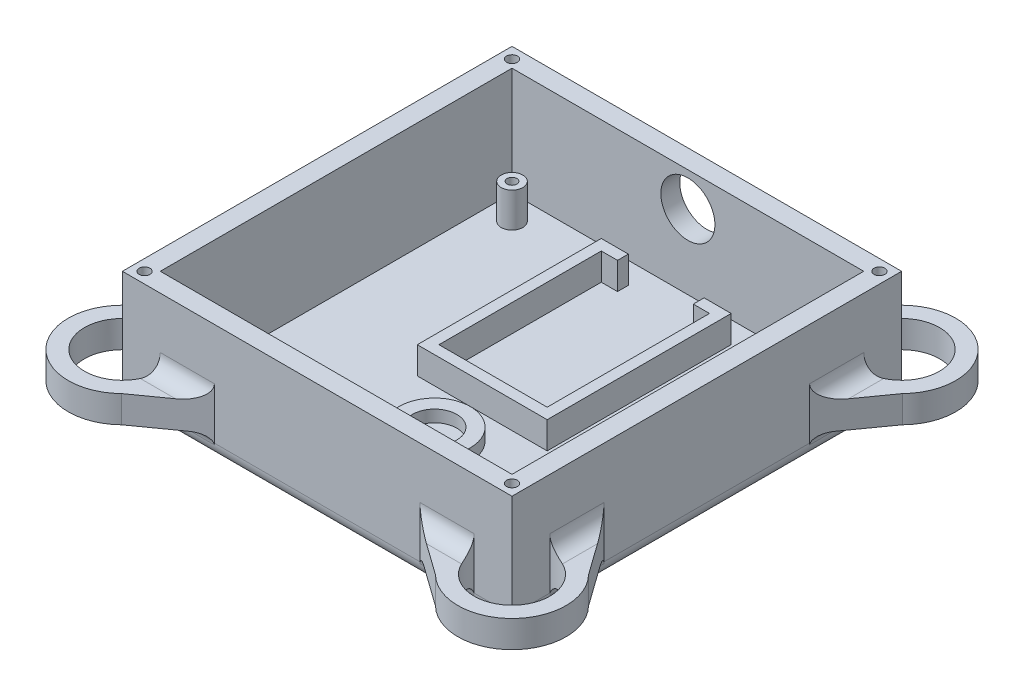
SolidWorks part; units mm, degrees
ref_plane "Front Plane" through (0, 0, 0) normal (0, 0, 1) x (1, 0, 0)
ref_plane "Top Plane" through (0, 0, 0) normal (0, 1, 0) x (1, 0, 0)
ref_plane "Right Plane" through (0, 0, 0) normal (1, 0, 0) x (0, 0, -1)
sketch "Sketch1" plane through (0, 0, 0) normal (0, 1, 0) x (1, 0, 0)
  line L2 (-35, 31) -> (30, 31)
  line L3 (30, 31) -> (30, -34)
  line L5 (-35, -34) -> (30, -34)
  line L6 (-35, 31) -> (-35, -34)
  line L7 (-1, 34.5) -> (33.5, 34.5)
  line L8 (33.5, 34.5) -> (-38.5, 34.5)
  line L9 (-38.5, 34.5) -> (-38.5, -37.5)
  line L11 (33.5, 34.5) -> (33.5, -37.5)
  line L12 (33.5, -37.5) -> (-38.5, -37.5)
  line L13 (0, -34) -> (0, -53.1946) construction
  dimension "D1" = 65
  dimension "D2" = 3.5
  dimension "D3" = 3.5
  dimension "D4" = 65
  dimension "D5" = 3.5
  dimension "D6" = 3.5
extrude "Boss-Extrude1" add sketch "Sketch1" along normal blind 20 contours L6 L2 L3 L5 L12 L11 L7 L8 L9 region at (16.25, 0, -33.4818)
sketch "Sketch2" plane through (0, 0, 0) normal (0, -1, 0) x (1, 0, 0)
  line L1 (-38.5, 37.5) -> (33.5, 37.5)
  line L2 (-38.5, 37.5) -> (-38.5, -34.5)
  line L3 (-38.5, -34.5) -> (33.5, -34.5)
  line L4 (33.5, 37.5) -> (33.5, -34.5)
extrude "Boss-Extrude2" add sketch "Sketch2" along normal blind 2
sketch "Sketch3" plane through (0, 0, 0) normal (0, 1, 0) x (1, 0, 0)
  line L0 (-2.5, 31) -> (-2.5, -34) construction
  line L1 (-35, 31) -> (30, 31) construction
  line L2 (-35, -34) -> (30, -34) construction
  line L3 (-2.5, -34) -> (-2.5, -1.5) construction
  line L4 (-2.5, -1.5) -> (30, -1.5) construction
  line L5 (30, 31) -> (30, -34) construction
  line L6 (30, -1.5) -> (-35, -1.5) construction
  line L7 (-35, 31) -> (-35, -34) construction
  line L8 (-32.5, 28.5) -> (27.5, 28.5) construction
  line L9 (27.5, 28.5) -> (27.5, -31.5) construction
  line L10 (-32.5, -31.5) -> (27.5, -31.5) construction
  line L11 (-32.5, 28.5) -> (-32.5, -31.5) construction
  circle A0 centre (25.5, 26.5) radius 2
  circle A1 centre (25.5, 26.5) radius 0.9
  circle A2 centre (25.5, -29.5) radius 2
  circle A3 centre (25.5, -29.5) radius 0.9
  circle A4 centre (-30.5, -29.5) radius 0.9
  circle A5 centre (-30.5, -29.5) radius 2
  circle A6 centre (-30.5, 26.5) radius 2
  circle A7 centre (-30.5, 26.5) radius 0.9
  point P23 (27.5, -1.5)
  point P28 (-2.5, -31.5)
  point P32 (-2.5, 28.5)
  dimension "D3" = 2
  dimension "D4" = 4
  dimension "D5" = 2
  dimension "D1" = 30
  dimension "D2" = 30
extrude "Boss-Extrude3" add sketch "Sketch3" along normal blind 6.4
sketch "Sketch4" plane through (0, 20, 0) normal (0, 1, 0) x (1, 0, 0)
  line L0 (-2.5, 34.5) -> (-2.5, -37.5) construction
  line L1 (-38.5, 34.5) -> (33.5, 34.5) construction
  line L2 (33.5, -37.5) -> (-38.5, -37.5) construction
  line L3 (-38.5, -1.5) -> (33.5, -1.5) construction
  line L5 (-38.5, 34.5) -> (-38.5, -37.5) construction
  line L7 (-35, 31) -> (-38.5, 34.5) construction
  line L9 (33.5, 34.5) -> (33.5, -37.5) construction
  circle A1 centre (-36.4494, 32.4494) radius 1
  circle A2 centre (31.4494, 32.4494) radius 1
  circle A3 centre (31.4494, -35.4494) radius 1
  circle A4 centre (-36.4494, -35.4494) radius 1
  dimension "D1" = 2.9
extrude "Cut-Extrude1" cut sketch "Sketch4" against normal blind 8
ref_plane "Plane1" through (0, 5, 0) normal (0, -1, 0) x (-1, 0, 0)
sketch "Sketch5" plane through (0, 5, 0) normal (0, 1, 0) x (1, 0, 0)
  line L0 (33.5, 34.5) -> (26.5, 41.1203) construction
  line L1 (33.5, 34.5) -> (26.5, 34.5)
  line L2 (26.5, 34.5) -> (26.5, 41.6414) construction
  line L3 (26.5, 34.5) -> (33.5, 34.5)
  line L5 (33.5, 34.5) -> (33.5, -37.5) construction
  line L6 (26.5, 34.5) -> (23.5, 34.5)
  line L7 (26.5, 41.6414) -> (26.5, 27.5) construction
  line L8 (33.5, 27.5) -> (33.5, 24.5)
  line L9 (-2.5, 38.4614) -> (-2.5, -44.4375) construction
  line L10 (-42.2092, -1.5) -> (36.5358, -1.5) construction
  line L14 (-31.5, 34.5) -> (-28.5, 34.5)
  line L19 (-38.5, 34.5) -> (33.5, 34.5) construction
  line L20 (26.5, 27.5) -> (40.6414, 27.5) construction
  line L21 (26.5, 41.6414) -> (16.5, 34.5)
  line L22 (16.5, 34.5) -> (23.5, 34.5)
  line L23 (40.6414, 27.5) -> (33.5, 17.5)
  line L24 (33.5, 17.5) -> (33.5, 24.5)
  line L25 (-21.5, 34.5) -> (-28.5, 34.5)
  line L26 (-31.5, 41.6414) -> (-21.5, 34.5)
  line L27 (-45.6414, 27.5) -> (-38.5, 17.5)
  line L28 (-38.5, 17.5) -> (-38.5, 24.5)
  line L29 (-38.5, 27.5) -> (-38.5, 24.5)
  line L30 (26.5, -37.5) -> (23.5, -37.5)
  line L31 (16.5, -37.5) -> (23.5, -37.5)
  line L32 (26.5, -44.6414) -> (16.5, -37.5)
  line L33 (40.6414, -30.5) -> (33.5, -20.5)
  line L34 (33.5, -20.5) -> (33.5, -27.5)
  line L35 (33.5, -30.5) -> (33.5, -27.5)
  line L36 (-38.5, -30.5) -> (-38.5, -27.5)
  line L37 (-38.5, -20.5) -> (-38.5, -27.5)
  line L38 (-45.6414, -30.5) -> (-38.5, -20.5)
  line L39 (-31.5, -44.6414) -> (-21.5, -37.5)
  line L40 (-21.5, -37.5) -> (-28.5, -37.5)
  line L41 (-31.5, -37.5) -> (-28.5, -37.5)
  arc A0 (33.5, 27.5) -> (26.5, 34.5) centre (33.5, 34.5) ccw
  arc A1 (40.6414, 27.5) -> (26.5, 41.6414) centre (33.5, 34.5) ccw
  arc A8 (-45.6414, 27.5) -> (-31.5, 41.6414) centre (-38.5, 34.5) cw
  arc A9 (-38.5, 27.5) -> (-31.5, 34.5) centre (-38.5, 34.5) cw
  arc A10 (40.6414, -30.5) -> (26.5, -44.6414) centre (33.5, -37.5) cw
  arc A11 (33.5, -30.5) -> (26.5, -37.5) centre (33.5, -37.5) cw
  arc A12 (-38.5, -30.5) -> (-31.5, -37.5) centre (-38.5, -37.5) ccw
  arc A13 (-45.6414, -30.5) -> (-31.5, -44.6414) centre (-38.5, -37.5) ccw
  dimension "D3" = 7
  dimension "D2" = 7
extrude "Boss-Extrude6" add sketch "Sketch5" along normal blind 2.5 and the other way blind 2.5 contours A9 L29 L28 L27 A8 L26 L25 L14 | A13 L38 L37 L36 A12 L41 L40 L39 | A1 L23 L24 L8 A0 L6 L22 L21 | A11 L35 L34 L33 A10 L32 L31 L30 region at (25, 5, -34.8818) region at (-43.7197, 5, -39.7197) region at (38.7197, 5, 42.7197) region at (-43.7197, 5, 42.7197)
sketch "Sketch10" plane through (0, 0, 0) normal (0, 1, 0) x (1, 0, 0)
  line L0 (-2.5, 31) -> (-2.5, -11.7) construction
  line L1 (-35, 31) -> (30, 31) construction
  line L4 (-35, 31) -> (-35, -34) construction
  line L5 (-35, -1.5) -> (30, -1.5) construction
  line L6 (30, 31) -> (30, -34) construction
  line L13 (-3.9, -19.6536) -> (-3.9, -22.2498)
  line L14 (-1.1, -19.6536) -> (-1.1, -22.2498)
  arc A0 (-1.1, -19.6536) -> (-3.9, -19.6536) centre (-2.5, -15.8) ccw
  arc A1 (-1.1, -22.2498) -> (-3.9, -22.2498) centre (-2.5, -15.8) ccw
  dimension "D2" = 8.2
  dimension "D1" = 13.2
  dimension "D3" = 14.3
extrude "Boss-Extrude7" add sketch "Sketch10" along normal blind 2.2
sketch "Sketch11" plane through (0, 0, 0) normal (0, 1, 0) x (1, 0, 0)
  line L0 (9.5, -1.5) -> (30, -1.5) construction
  line L1 (-12.5, 25) -> (-12.5, -5)
  line L2 (-35, -34) -> (30, -34) construction
  line L3 (-14.5, 27) -> (-14.5, -7)
  line L5 (30, 31) -> (30, -34) construction
  line L6 (-35, 31) -> (30, 31) construction
  line L7 (-12.5, 25) -> (-9.5, 25)
  line L9 (-12.5, -5) -> (7.5, -5)
  line L12 (-14.5, -7) -> (9.5, -7)
  line L13 (9.5, -7) -> (9.5, 27)
  line L14 (9.5, 27) -> (4.5, 27)
  line L15 (4.5, 27) -> (4.5, 25)
  line L16 (7.5, 25) -> (7.5, -5)
  line L17 (-2.5, -5) -> (7.5, -5)
  line L19 (4.5, 25) -> (7.5, 25)
  line L21 (-14.5, 27) -> (-9.5, 27)
  line L22 (-9.5, 27) -> (-9.5, 25)
  line L23 (-9.5, 25) -> (-12.5, 25)
  line L24 (4.5, 25) -> (7.5, 25)
  line L25 (-2.5, -7) -> (-2.5, -34) construction
  dimension "D1" = 30
  dimension "D2" = 6
  dimension "D3" = 10
  dimension "D4" = 2
  dimension "D6" = 2
fillet "Fillet1" radius 3 4 edges at (-2.5, -2, 37.5) (33.5, -2, 1.5) (-2.5, -2, -34.5) (-38.5, -2, 1.5)
extrude "Boss-Extrude8" add sketch "Sketch11" along normal blind 5 contours L22 L21 L3 L12 L13 L14 L15 L19 L16 L9 L1 L7 region at (-12.9162, 0, -10)
fillet "Fillet2" radius 3 8 edges at (-38.5, 7.5, -22.5) (-26.5, 7.5, -34.5) (21.5, 7.5, -34.5) (33.5, 7.5, -22.5) (33.5, 7.5, 25.5) (21.5, 7.5, 37.5) (-38.5, 7.5, 25.5) (-26.5, 7.5, 37.5)
fillet "Fillet3" radius 2 8 edges at (21.5, 2.5, 37.5) (33.5, 2.5, 25.5) (33.5, 2.5, -22.5) (21.5, 2.5, -34.5) (-26.5, 2.5, -34.5) (-38.5, 2.5, -22.5) (-26.5, 2.5, 37.5) (-38.5, 2.5, 25.5)
sketch "Sketch15" plane through (0, 0, -34.5) normal (0, 0, -1) x (-1, 0, 0)
  line L0 (38.5, 20) -> (-33.5, 20) construction
  line L1 (2.5, 20) -> (2.5, 1) construction
  line L2 (-16.5, 1) -> (21.5, 1) construction
  circle A1 centre (2.5, 13.7) radius 5
  dimension "D1" = 6.3
extrude "Cut-Extrude2" cut sketch "Sketch15" against normal blind 5
